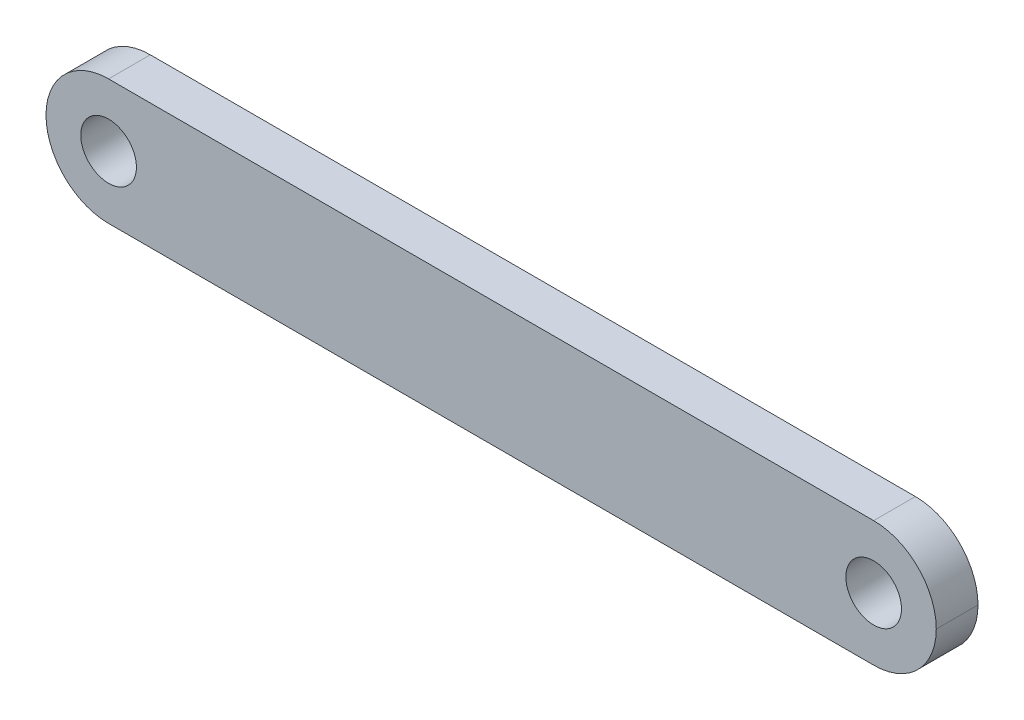
SolidWorks part; units mm, degrees
ref_plane "Front" through (0, 0, 0) normal (0, 0, 1) x (1, 0, 0)
ref_plane "Top" through (0, 0, 0) normal (0, 1, 0) x (1, 0, 0)
ref_plane "Right" through (0, 0, 0) normal (1, 0, 0) x (0, 0, -1)
sketch "Esquisse1" plane through (0, 0, 0) normal (0, 0, 1) x (1, 0, 0)
  line L0 (0, 9) -> (9, 9) construction
  line L1 (0, 0) -> (128, 0)
  line L2 (0, 0) -> (0, 18)
  line L3 (0, 18) -> (128, 18)
  line L4 (128, 0) -> (128, 18)
  line L5 (64, 0) -> (64, 18) construction
  circle A0 centre (9, 9) radius 4
  circle A1 centre (119, 9) radius 4
  dimension "D2" = 8
  dimension "D4" = 110
  dimension "D1" = 18
  dimension "D3" = 9
extrude "Boss.-Extru.1" add sketch "Esquisse1" along normal blind 6
fillet "Congé1" radius 9 4 edges at (128, 18, 3) (128, 0, 3) (0, 0, 3) (0, 18, 3)
